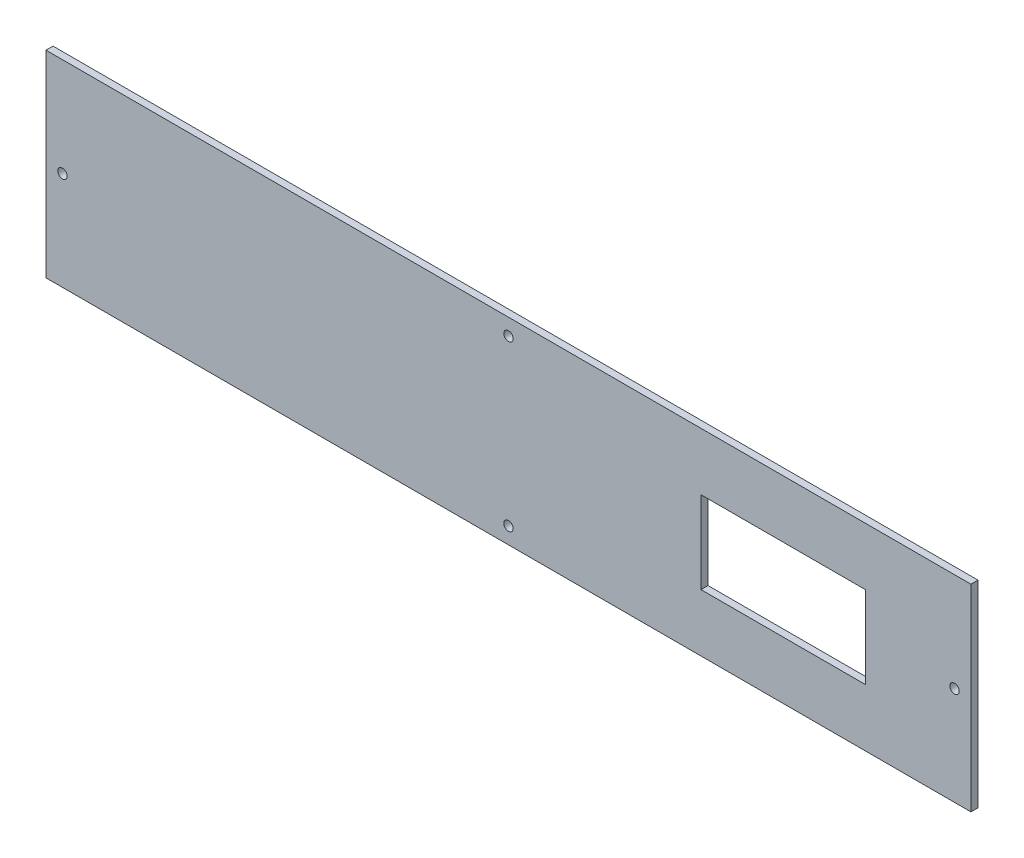
SolidWorks part; units mm, degrees
ref_plane "Piano frontale" through (0, 0, 0) normal (0, 0, 1) x (1, 0, 0)
ref_plane "Piano superiore" through (0, 0, 0) normal (0, 1, 0) x (1, 0, 0)
ref_plane "Piano destro" through (0, 0, 0) normal (1, 0, 0) x (0, 0, -1)
sketch "f" plane through (0, 0, 0) normal (0, 0, 1) x (1, 0, 0)
  line L0 (0, 0) -> (0, 84)
  line L1 (0, 84) -> (394, 84)
  line L2 (394, 84) -> (394, 0)
  line L3 (394, 0) -> (0, 0)
  line L4 (0, 42) -> (394, 42) construction
  line L5 (197, 42) -> (197, 123.488) construction
  line L6 (279, 59.5) -> (279, 24.5)
  line L7 (279, 24.5) -> (349, 24.5)
  line L8 (349, 24.5) -> (349, 59.5)
  line L9 (349, 59.5) -> (279, 59.5)
  circle A0 centre (7, 42) radius 2
  circle A1 centre (197, 77) radius 2
  circle A2 centre (197, 7) radius 2
  circle A3 centre (387, 42) radius 2
  dimension "D3" = 7
  dimension "D4" = 7
  dimension "D6" = 4
  dimension "D1" = 84
  dimension "D2" = 394
  dimension "D5" = 45
  dimension "D7" = 70
  dimension "D8" = 35
extrude "Estrusione-Estrusione1" add sketch "f" along normal blind 3
